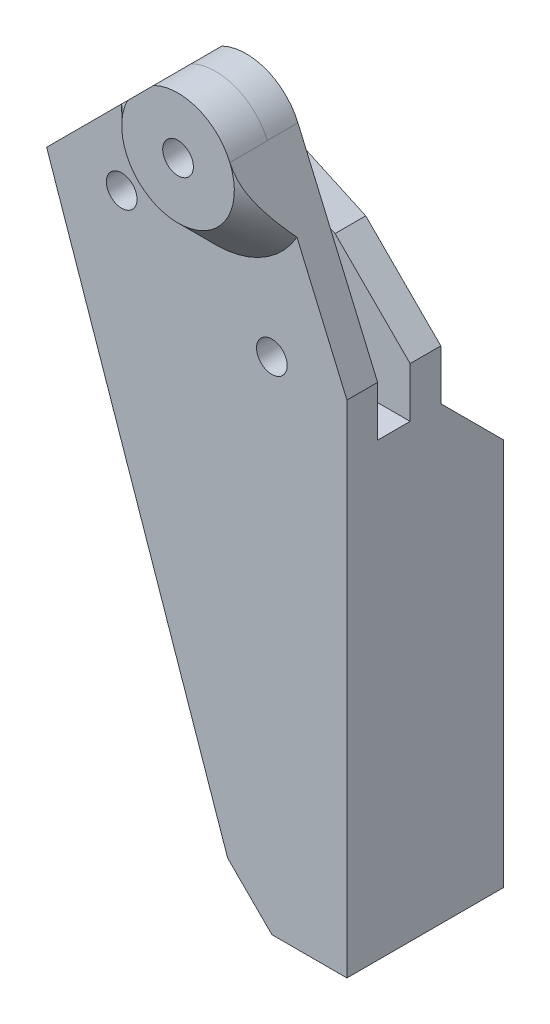
SolidWorks part; units mm, degrees
material "ABS"
ref_plane "Płaszczyzna przednia" through (0, 0, 0) normal (0, 0, 1) x (1, 0, 0)
ref_plane "Płaszczyzna górna" through (0, 0, 0) normal (0, 1, 0) x (1, 0, 0)
ref_plane "Płaszczyzna prawa" through (0, 0, 0) normal (1, 0, 0) x (0, 0, -1)
sketch "Szkic1" plane through (0, 0, 0) normal (0, 0, 1) x (1, 0, 0)
  line L0 (-24, 11) -> (-24, 23)
  line L1 (-24, 11) -> (-36, 11)
  line L2 (-24, 23) -> (-36, 11)
  line L3 (0, 0) -> (0, 12)
  line L4 (0, 12) -> (-24, 23)
  line L5 (0, 0) -> (12, 0)
  line L6 (0, 12) -> (12, 0)
  line L7 (0, 0) -> (0, -80)
  line L8 (0, -80) -> (12, -80)
  line L9 (0, -80) -> (-7.0711, -72.9289)
  line L10 (-7.0711, -72.9289) -> (-36, 11)
  line L11 (12, -80) -> (12, 0)
  circle A0 centre (0, 0) radius 2.45
  circle A1 centre (-24, 11) radius 2.45
  dimension "D1" = 4.9
  dimension "D2" = 24
  dimension "D3" = 4.9
  dimension "D4" = 11
  dimension "D5" = 12
  dimension "D6" = 12
  dimension "D7" = 12
  dimension "D8" = 12
  dimension "D9" = 80
  dimension "D10" = 12
  dimension "D11" = 135
  dimension "D12" = 10
extrude "Dodanie-wyciągnięcie1" add sketch "Szkic1" along normal blind 25 contours A1 L0 L2 L1 | A1 L1 L10 L9 L7 A0 L3 L4 L0 | A0 L5 L6 L3 | A0 L7 L8 L11 L5 region at (-28.2074, 15.2074, 0) region at (-12.4707, -19.6827, 0) region at (4.2074, 4.2074, 0) region at (6.0245, -40.1923, 0)
sketch "Szkic3" plane through (12, 0, 0) normal (1, 0, 0) x (0, 0, -1)
  line L0 (-20.1, 17) -> (-20.1, -8)
  line L1 (-25, -80) -> (-25, 0) construction
  line L2 (-14.9, 17) -> (-14.9, -8)
  line L3 (-10, 17) -> (-10, -8)
  line L4 (-5, 17) -> (-5, -8)
  line L5 (0, -80) -> (0, 0) construction
  line L6 (-25, -8) -> (0, -8)
  line L7 (-25, 0) -> (0, 0) construction
  line L8 (-25, 17) -> (0, 17)
  line L9 (-25, 12) -> (-25, 0) construction
  line L10 (0, 12) -> (0, 0) construction
  line M8 (0, 0) -> (-25, 0)
  dimension "D1" = 4.9
  dimension "D2" = 10.1
  dimension "D3" = 5
  dimension "D4" = 10
  dimension "D5" = 8
  dimension "D6" = 25
extrude "Wytnij-wyciągnięcie1" cut sketch "Szkic3" against normal blind 20 contours L8 L0 L2 M8 | L0 L6 L2 M8 | L8 L3 L4 M8 | L3 L6 L4 M8 region at (12, 8.5, 17.5) region at (12, -4, 17.5) region at (12, 8.5, 7.5) region at (12, -4, 7.5)
sketch "Szkic4" plane through (12, 0, 0) normal (1, 0, 0) x (0, 0, -1)
  line L5 (-10, 12) -> (-10, 0) construction
  line L6 (-10, 4) -> (-5, 4)
  line L7 (-10, 4) -> (-10, 23)
  line L8 (-10, 23) -> (-5, 23)
  line L9 (-5, 4) -> (-5, 23)
  line L10 (-25, 23) -> (0, 23) construction
  dimension "D1" = 5
  dimension "D2" = 19
extrude "Wytnij-wyciągnięcie2" cut sketch "Szkic4" against normal blind 58
chamfer "Sfazowanie1" distance 6 angle 45 1 edges at (-8, -8, 17.5)
chamfer "Sfazowanie2" distance 12 angle 45 1 edges at (-8, 4, 7.5)
chamfer "Sfazowanie3" distance 2 angle 30 2 edges at (-8, 6.8333, 14.9) (-8, 6.8333, 20.1) first distance on face at (-8, 6.8333, 17.5)
sketch "Szkic5" plane through (0, 0, 25) normal (0, 0, 1) x (1, 0, 0)
  line L0 (-24, 23) -> (-12.8786, 34.1212)
  line L1 (-24, 23) -> (0, 12)
  line L4 (12, 0) -> (-0.7344, 29.5607)
  line L7 (12, 0) -> (0, 12)
  circle A0 centre (-9, 26) radius 2.45
  arc A5 (-0.7344, 29.5607) -> (-12.8786, 34.1212) centre (-9, 26) ccw
  line M11 (0, 12) -> (-24, 23)
  dimension "D3" = 4.9
  dimension "D1" = 26
  dimension "D2" = 9
extrude "Dodanie-wyciągnięcie2" add sketch "Szkic5" against normal blind 4.9 contours A0 M11 | A0 M11 region at (-6.0985, 21.7847, 25)
sketch "Szkic6" plane through (12, 0, 0) normal (1, 0, 0) x (0, 0, -1)
  line L1 (-10, -8) -> (0, -8)
  line L2 (-10, -8) -> (-10, 23)
  line L3 (-10, 23) -> (0, 23)
  line L4 (0, -8) -> (0, 23)
extrude "Wytnij-wyciągnięcie3" cut sketch "Szkic6" against normal blind 60
chamfer "Sfazowanie4" distance 10 angle 45 1 edges at (-8.7255, -8, 0)
sketch "Szkic8" plane through (0, 0, 25) normal (0, 0, 1) x (1, 0, 0)
  line L0 (-17.1214, 29.8785) -> (-12.8784, 34.1214)
  circle A0 centre (-9, 26) radius 2.45
  arc A1 (-17.1214, 29.8785) -> (-12.8784, 34.1214) centre (-9, 26) ccw
  dimension "D1" = 18
  dimension "D2" = 4.9
extrude "Dodanie-wyciągnięcie3" add sketch "Szkic8" along normal blind 6
chamfer "Sfazowanie5" distance 6 angle 45 1 edges at (-9.196, 17.0021, 25)
sketch "Szkic10" plane through (12, 0, 0) normal (1, 0, 0) x (0, 0, -1)
  line L0 (-20, -23) -> (-20, -75)
  line L1 (-20, -75) -> (-5, -75)
  line L2 (-5, -75) -> (-5, -23)
  line L3 (-5, -23) -> (-20, -23)
  line L4 (-25, -80) -> (0, -80) construction
  line L5 (0, -80) -> (0, -18) construction
  line L6 (-25, -80) -> (-25, 0) construction
  dimension "D1" = 5
  dimension "D2" = 5
  dimension "D3" = 5
  dimension "D4" = 5
extrude "Wytnij-wyciągnięcie6" cut sketch "Szkic10" against normal blind 70 from offset 5 offset against normal yes
chamfer "Sfazowanie9" distance 7 angle 60 4 edges at (7, -49, 20) (7, -75, 12.5) (7, -49, 5) (7, -23, 12.5) first distance on face at (7, -49, 12.5)
chamfer "Sfazowanie10" distance 3 angle 45 1 edges at (-15.4226, 19.0687, 20.1)
